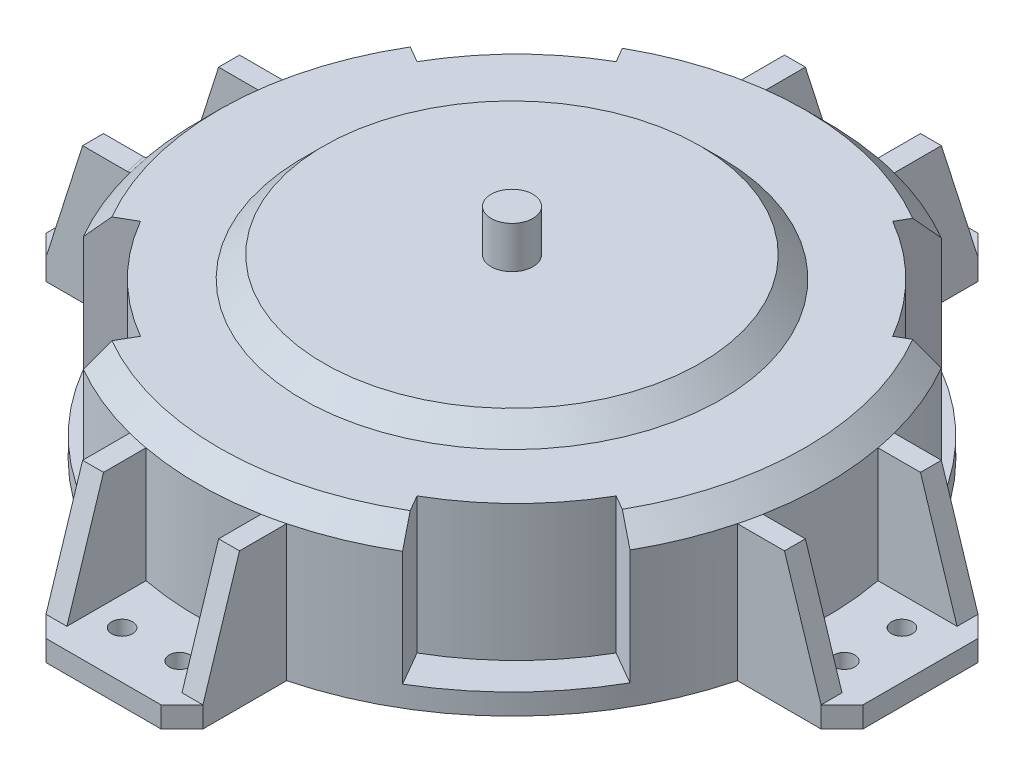
SolidWorks part; units mm, degrees
ref_plane "Front Plane" through (0, 0, 0) normal (0, 0, 1) x (1, 0, 0)
ref_plane "Top Plane" through (0, 0, 0) normal (0, 1, 0) x (1, 0, 0)
ref_plane "Right Plane" through (0, 0, 0) normal (1, 0, 0) x (0, 0, -1)
sketch "Sketch1" plane through (0, 0, 0) normal (0, 1, 0) x (1, 0, 0)
  circle A0 centre (0, 0) radius 150
  dimension "D1" = 300
extrude "Boss-Extrude1" add sketch "Sketch1" along normal blind 75
chamfer "Chamfer1" distance 10 angle 45 1 edges at (0, 75, 150)
sketch "Sketch2" plane through (0, 75, 0) normal (0, 1, 0) x (1, 0, 0)
  line L0 (-150, 0) -> (-195.2369, 0) construction
  line L1 (-195.2369, -37.5) -> (-195.2369, 37.5)
  line L2 (-195.2369, 37.5) -> (-145.2369, 37.5)
  line L3 (-195.2369, -37.5) -> (-145.2369, -37.5)
  circle A0 centre (0, 0) radius 150 construction
  arc A1 (-145.2369, 37.5) -> (-145.2369, -37.5) centre (0, 0) ccw
  point P6 (-195.2369, 0)
  dimension "D1" = 50
  dimension "D2" = 75
extrude "Boss-Extrude2" add sketch "Sketch2" along normal blind 10 from offset 75 offset against normal yes
chamfer "Chamfer2" distance 10 angle 45 2 edges at (-195.2369, 5, -37.5) (-195.2369, 5, 37.5)
sketch "Sketch3" plane through (0, 0, 37.5) normal (0, 0, 1) x (1, 0, 0)
  line L0 (-145.2369, 0) -> (-145.2369, 65)
  line L1 (-150, 65) -> (150, 65) construction
  line L2 (-145.2369, 65) -> (-167.7369, 65)
  line L3 (-167.7369, 65) -> (-185.2369, 10)
  line L4 (-185.2369, 10) -> (-185.2369, 0)
  line L5 (-185.2369, 0) -> (-145.2369, 0)
  dimension "D1" = 17.5
extrude "Boss-Extrude3" add sketch "Sketch3" against normal blind 10
sketch "Sketch4" plane through (0, 10, 0) normal (0, 1, 0) x (1, 0, 0)
  line L0 (-195.2369, 0) -> (-150, 0) construction
  line L2 (-195.2369, 27.5) -> (-195.2369, -27.5) construction
  line L3 (-172.6184, 0) -> (-172.6184, -27.5) construction
  line L5 (-185.2369, -27.5) -> (-147.4576, -27.5) construction
  arc A0 (-145.2369, 37.5) -> (-147.4576, -27.5) centre (0, 0) ccw construction
  circle A1 centre (-172.6184, -13.75) radius 5
  dimension "D1" = 10
extrude "Cut-Extrude1" cut sketch "Sketch4" against normal blind 10
ref_plane "Plane1" through (0, 0, 0) normal (0, 0, -1) x (-1, 0, 0)
mirror "Mirror2" about plane through (0, 0, 0) normal (0, 0, -1) of "Cut-Extrude1", "Boss-Extrude3"
fillet "Fillet1" radius 2.5 2 edges at (-166.3472, 10, -27.5) (-185.2369, 10, -32.5)
fillet "Fillet2" radius 2.5 2 edges at (-185.2369, 10, 32.5) (-166.3472, 10, 27.5)
fillet "Fillet3" radius 2.5 2 edges at (-146.4326, 65, 32.519) (-146.4326, 65, -32.519)
pattern_circular "CirPattern4" count 4 over 360 about axis through (0, 0, 0) along (0, 1, 0) of "Mirror2", "Boss-Extrude2", "Chamfer2", "Boss-Extrude3", "Cut-Extrude1"
sketch "Sketch5" plane through (0, 75, 0) normal (0, 1, 0) x (1, 0, 0)
  line L0 (150, 0) -> (130, 0) construction
  line L1 (0, 150) -> (0, -150) construction
  line L2 (-112.5833, -65) -> (-129.9038, -75)
  line L3 (-65, -112.5833) -> (-75, -129.9038)
  line L4 (0, 0) -> (-150, 0) construction
  arc A1 (-129.9038, -75) -> (-75, -129.9038) centre (0, 0) ccw
  circle A2 centre (0, 0) radius 130
  arc A3 (-112.5833, -65) -> (-65, -112.5833) centre (0, 0) ccw
  dimension "D2" = 30
  dimension "D3" = 30
  dimension "D1" = 10
extrude "Cut-Extrude2" cut sketch "Sketch5" against normal blind 65
pattern_circular "CirPattern5" count 4 over 360 about axis through (1.0964, 0, -1.0964) along (0, 1, 0) of "Cut-Extrude2"
sketch "Sketch6" plane through (0, 75, 0) normal (0, 1, 0) x (1, 0, 0)
  circle A0 centre (0, 0) radius 100
  dimension "D1" = 200
extrude "Boss-Extrude4" add sketch "Sketch6" along normal blind 10
chamfer "Chamfer3" distance 10 angle 45 1 edges at (0, 85, 100)
sketch "Sketch7" plane through (0, 85, 0) normal (0, 1, 0) x (1, 0, 0)
  circle A0 centre (0, 0) radius 10
  dimension "D1" = 20
extrude "Boss-Extrude5" add sketch "Sketch7" along normal blind 20
